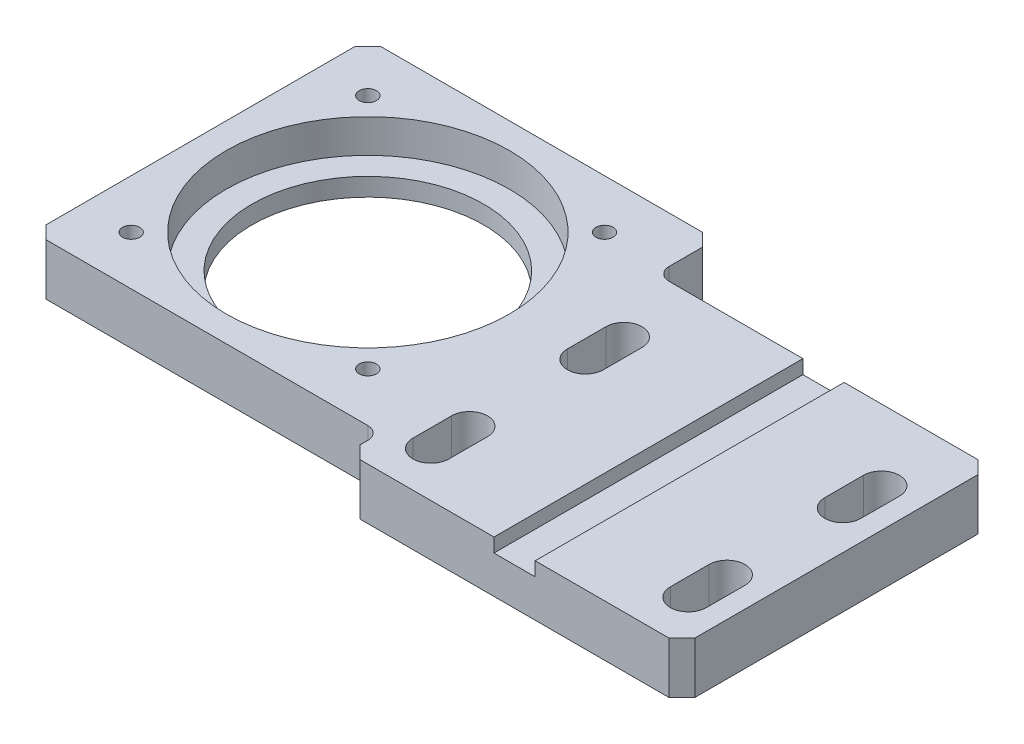
SolidWorks part; units mm, degrees
ref_plane "前视基准面" through (0, 0, 0) normal (0, 0, 1) x (1, 0, 0)
ref_plane "上视基准面" through (0, 0, 0) normal (0, 1, 0) x (1, 0, 0)
ref_plane "右视基准面" through (0, 0, 0) normal (1, 0, 0) x (0, 0, -1)
sketch "草图2" plane through (0, 0, 0) normal (0, 1, 0) x (1, 0, 0)
  line L0 (0, 0) -> (135, 0)
  line L1 (135, 0) -> (135, -23)
  line L2 (135, -23) -> (265, -23)
  line L3 (265, -23) -> (265, -143)
  line L4 (265, -143) -> (135, -143)
  line L5 (135, -143) -> (135, -130)
  line L6 (135, -130) -> (0, -130)
  line L7 (0, -130) -> (0, 0)
  point P9 (200, -143)
  dimension "D1" = 130
  dimension "D2" = 120
  dimension "D3" = 143
  dimension "D4" = 135
  dimension "D5" = 130
extrude "凸台-拉伸1" add sketch "草图2" along normal blind 20
sketch "草图3" plane through (0, 20, 0) normal (0, 1, 0) x (1, 0, 0)
  line L0 (0, 0) -> (0, -130) construction
  circle A0 centre (65, -65) radius 45
  point P5 (0, -65)
  dimension "D1" = 90
  dimension "D2" = 65
extrude "切除-拉伸1" cut sketch "草图3" against normal through all
sketch "草图4" plane through (0, 20, 0) normal (0, 1, 0) x (1, 0, 0)
  circle A0 centre (65, -65) radius 55
  dimension "D1" = 110
extrude "切除-拉伸2" cut sketch "草图4" against normal blind 13
sketch "草图5" plane through (0, 20, 0) normal (0, 1, 0) x (1, 0, 0)
  line L0 (192, -23) -> (192, -143)
  line L1 (265, -23) -> (135, -23) construction
  line L2 (135, -143) -> (265, -143) construction
  line L3 (208, -23) -> (208, -143)
  line L4 (200, -23) -> (200, -143) construction
  line L5 (265, -143) -> (265, -23) construction
  line L6 (192, -23) -> (208, -23)
  line L7 (208, -143) -> (192, -143)
  dimension "D1" = 65
  dimension "D2" = 16
extrude "切除-拉伸3" cut sketch "草图5" against normal blind 5.4
sketch "草图6" plane through (0, 20, 0) normal (0, 1, 0) x (1, 0, 0)
  line L0 (250, -110.5) -> (250, -125.5) construction
  line L2 (257, -110.5) -> (257, -125.5)
  line L5 (243, -110.5) -> (243, -125.5)
  line L11 (208, -143) -> (265, -143) construction
  line L14 (200, -23) -> (200, -143) construction
  line L17 (208, -23) -> (192, -23) construction
  line L18 (192, -143) -> (208, -143) construction
  arc A8 (257, -110.5) -> (243, -110.5) centre (250, -110.5) ccw
  arc A9 (243, -125.5) -> (257, -125.5) centre (250, -125.5) ccw
  point P2 (250, -118)
  point P9 (250, -132.5)
  point P10 (250, -103.5)
  dimension "D2" = 29
  dimension "D1" = 10.5
  dimension "D3" = 14
  dimension "D4" = 50
extrude "切除-拉伸4" cut sketch "草图6" against normal through all
pattern_linear "阵列(线性)1" count 2 spacing 60 along (0, 0, -1) count 2 spacing 100 along (-1, 0, 0) of "切除-拉伸4"
fillet "圆角1" radius 5 2 edges at (135, 10, 23) (135, 10, 130)
chamfer "倒角1" distance 5 6 edges at (265, 10, 23) (265, 10, 143) (135, 10, 143) (135, 10, 0) (0, 10, 130) (0, 10, 0)
sketch "草图7" plane through (0, 20, 0) normal (0, 1, 0) x (1, 0, 0)
  line L0 (65, -65) -> (65, 25.1133) construction
  line L1 (65, -65) -> (110.9619, -19.0381) construction
  circle A1 centre (65, -65) radius 65 construction
  circle A2 centre (110.9619, -19.0381) radius 3.35
  circle A3 centre (110.9619, -110.9619) radius 3.35
  circle A4 centre (19.0381, -110.9619) radius 3.35
  circle A5 centre (19.0381, -19.0381) radius 3.35
  point P15 (65, -65)
  dimension "D1" = 130
  dimension "D2" = 6.7
  dimension "D3" = 45
  dimension "D4" = 4
extrude "切除-拉伸5" cut sketch "草图7" against normal through all
